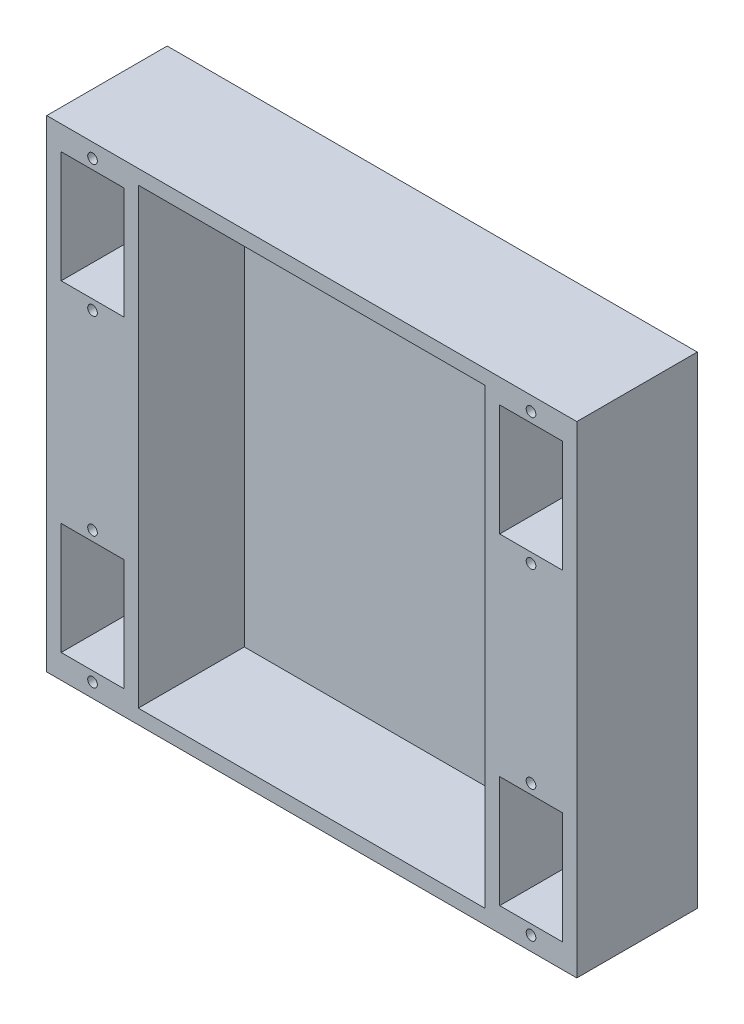
SolidWorks part; units mm, degrees
ref_plane "Plano frontal" through (0, 0, 0) normal (0, 0, 1) x (1, 0, 0)
ref_plane "Plano superior" through (0, 0, 0) normal (0, 1, 0) x (1, 0, 0)
ref_plane "Plano direito" through (0, 0, 0) normal (1, 0, 0) x (0, 0, -1)
sketch "Esboço1" plane through (0, 0, 0) normal (0, 0, 1) x (1, 0, 0)
  line L0 (45.5, 47.05) -> (45.5, 19.75) construction
  line L1 (-55, 50) -> (55, 50)
  line L2 (-55, 50) -> (-55, -50)
  line L3 (-55, -50) -> (55, -50)
  line L4 (55, 50) -> (55, -50)
  line L5 (-55, 50) -> (55, -50) construction
  line L6 (-55, -50) -> (55, 50) construction
  line L7 (39, 45) -> (52, 45)
  line L8 (39, 45) -> (39, 21.8)
  line L9 (39, 21.8) -> (52, 21.8)
  line L10 (52, 45) -> (52, 21.8)
  line L11 (39, 45) -> (52, 21.8) construction
  line L12 (39, 21.8) -> (52, 45) construction
  line L13 (-11.651, 0) -> (14.1427, 0) construction
  line L14 (0, 12.3596) -> (0, -15.2082) construction
  line L15 (39, -21.8) -> (52, -45) construction
  line L16 (39, -45) -> (52, -21.8) construction
  line L17 (45.5, -47.05) -> (45.5, -19.75) construction
  line L18 (52, -45) -> (52, -21.8)
  line L19 (39, -21.8) -> (52, -21.8)
  line L20 (39, -45) -> (39, -21.8)
  line L21 (39, -45) -> (52, -45)
  line L22 (-45.5, -47.05) -> (-45.5, -19.75) construction
  line L23 (-39, -45) -> (-52, -21.8) construction
  line L24 (-39, -21.8) -> (-52, -45) construction
  line L25 (-39, 21.8) -> (-52, 45) construction
  line L26 (-39, 45) -> (-52, 21.8) construction
  line L27 (-45.5, 47.05) -> (-45.5, 19.75) construction
  line L28 (-39, -45) -> (-52, -45)
  line L29 (-39, -45) -> (-39, -21.8)
  line L30 (-39, -21.8) -> (-52, -21.8)
  line L31 (-52, -45) -> (-52, -21.8)
  line L32 (-52, 45) -> (-52, 21.8)
  line L33 (-39, 21.8) -> (-52, 21.8)
  line L34 (-39, 45) -> (-39, 21.8)
  line L35 (-39, 45) -> (-52, 45)
  line L37 (0.2789, -11.1404) -> (0.2789, 35.8596) construction
  line L38 (0.2789, -11.1404) -> (35.2789, -11.1404) construction
  line L39 (35.2789, -11.1404) -> (35.2789, 35.8596) construction
  line L40 (0.2789, 35.8596) -> (35.2789, 35.8596) construction
  line L41 (0.2789, -11.1404) -> (35.2789, 35.8596) construction
  line L42 (35.2789, -11.1404) -> (0.2789, 35.8596) construction
  line L43 (-31.1, -20.1621) -> (31.1, -20.1621) construction
  line L44 (-31.1, -20.1621) -> (-31.1, -42.4621) construction
  line L45 (-31.1, -42.4621) -> (31.1, -42.4621) construction
  line L46 (31.1, -20.1621) -> (31.1, -42.4621) construction
  line L47 (-31.1, -20.1621) -> (31.1, -42.4621) construction
  line L48 (-31.1, -42.4621) -> (31.1, -20.1621) construction
  circle A0 centre (45.5, 19.75) radius 1
  circle A1 centre (45.5, 47.05) radius 1
  circle A2 centre (45.5, 38.5) radius 6.5 construction
  circle A3 centre (45.5, -38.5) radius 6.5 construction
  circle A4 centre (45.5, -47.05) radius 1
  circle A5 centre (45.5, -19.75) radius 1
  circle A6 centre (-45.5, -38.5) radius 6.5 construction
  circle A7 centre (-45.5, 38.5) radius 6.5 construction
  circle A8 centre (-45.5, -19.75) radius 1
  circle A9 centre (-45.5, -47.05) radius 1
  circle A10 centre (-45.5, 47.05) radius 1
  circle A11 centre (-45.5, 19.75) radius 1
  point P0 (0, 0)
  point P6 (45.5, 33.4)
  point P18 (45.5, 33.4)
  point P22 (2.2694, -31.3121)
  point P33 (45.5, -33.4)
  point P54 (-45.5, -33.4)
  point P55 (-45.5, 33.4)
  point P56 (17.7789, 12.3596)
  point P61 (0, -31.3121)
  point P66 (0, 0)
  point P67 (-26.8441, -1.4243)
  point P68 (3.3994, 26.2509)
  point P69 (-20.8487, 4.0012)
  point P70 (-21.2484, 0)
  point P71 (15.5495, 20.7923)
  point P72 (17.7789, 12.3596)
  dimension "D4" = 2
  dimension "D1" = 23.2
  dimension "D2" = 13
  dimension "D3" = 3
  dimension "D5" = 27.3
  dimension "D6" = 5
  dimension "D7" = 47
  dimension "D8" = 35
  dimension "D9" = 62.2
  dimension "D10" = 22.3
  dimension "D11" = 110
  dimension "D12" = 100
extrude "Ressalto-extrusão1" add sketch "Esboço1" along normal blind 25
sketch "Esboço3" plane through (0, 0, 25) normal (0, 0, 1) x (1, 0, 0)
  line L0 (-39, 33.4) -> (-36, 33.4) construction
  line L1 (-36, 47) -> (36, 47)
  line L2 (-36, 47) -> (-36, -47)
  line L3 (-36, -47) -> (36, -47)
  line L4 (36, 47) -> (36, -47)
  line L5 (-39, 21.8) -> (-39, 45) construction
  line L7 (39, 33.4) -> (36, 33.4) construction
  line L8 (39, 45) -> (39, 21.8) construction
  line L9 (0, 50) -> (0, 47) construction
  line L12 (55, 50) -> (-55, 50) construction
  line L13 (0, -50) -> (0, -47) construction
  line L14 (-55, -50) -> (55, -50) construction
  dimension "D1" = 3
  dimension "D2" = 3
extrude "Corte-extrusão1" cut sketch "Esboço3" against normal offset from surface (22 mm away) 3 up to face at (-45.5, -33.4, 0)
sketch "Esboço4" plane through (0, 0, 0) normal (0, 0, -1) x (-1, 0, 0)
  line L0 (-52, -45) -> (-52, -21.8) construction
  line L1 (55, 50) -> (-55, 50)
  line L2 (55, 50) -> (55, -50)
  line L3 (55, -50) -> (-55, -50)
  line L4 (-55, 50) -> (-55, -50)
  line L5 (55, 50) -> (-55, -50) construction
  line L6 (55, -50) -> (-55, 50) construction
  line L7 (-39, -45) -> (-52, -45) construction
  line L9 (-14.847, 0) -> (0, 0) construction
  line L10 (0, -11.1268) -> (0, 0) construction
  circle A0 centre (-45.5, -39.05) radius 1.6
  circle A1 centre (-45.5, 39.05) radius 1.6
  circle A2 centre (45.5, 39.05) radius 1.6
  circle A3 centre (45.5, -39.05) radius 1.6
  point P0 (0, 0)
  point P11 (-52, -33.4)
  point P15 (-45.5, -45)
  dimension "D2" = 3.2
  dimension "D1" = 5.65
extrude "Ressalto-extrusão2" add sketch "Esboço4" against normal blind 2.5
